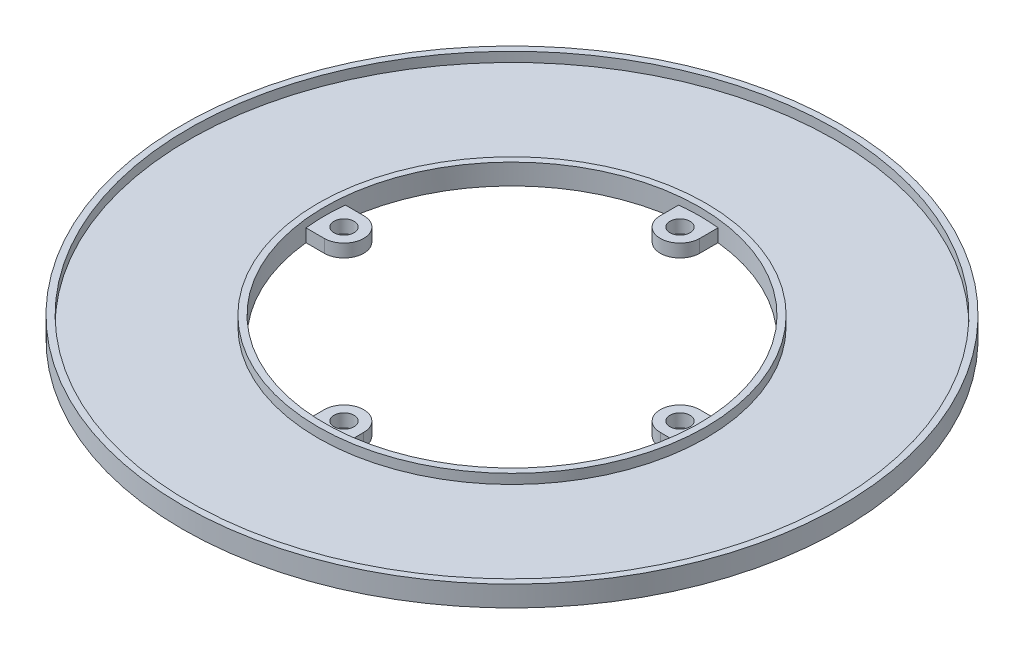
SolidWorks part; units mm, degrees
ref_plane "前视基准面" through (0, 0, 0) normal (0, 0, 1) x (1, 0, 0)
ref_plane "上视基准面" through (0, 0, 0) normal (0, 1, 0) x (1, 0, 0)
ref_plane "右视基准面" through (0, 0, 0) normal (1, 0, 0) x (0, 0, -1)
other "Configuration Table"
sketch "草图1" plane through (0, 0, 0) normal (0, 0, 1) x (1, 0, 0)
  line L0 (29, 0) -> (29, 3.2)
  line L1 (29, 3.2) -> (30, 3.2)
  line L2 (30, 3.2) -> (30, 1.7)
  line L3 (30, 1.7) -> (50, 1.7)
  line L4 (50, 1.7) -> (50, 3.2)
  line L5 (50, 3.2) -> (51, 3.2)
  line L6 (51, 3.2) -> (51, 0)
  line L7 (51, 0) -> (29, 0)
  line L8 (0, 0) -> (0, 3.2) construction
  point P2 (40, 1.7)
  point P9 (40, 0)
  point P11 (0, 0)
  dimension "D1" = 29
  dimension "D2" = 51
  dimension "D3" = 20
  dimension "D4" = 1.7
  dimension "D5" = 1.5
revolve "旋转1" add sketch "草图1" angle 360 about L8
sketch "草图2" plane through (0, 0, 0) normal (0, -1, 0) x (1, 0, 0)
  line L0 (-3.05, 26) -> (-3.05, 28.8392)
  line L1 (3.05, 26) -> (3.05, 28.8392)
  line L2 (26, 3.05) -> (28.8392, 3.05)
  line L3 (26, -3.05) -> (28.8392, -3.05)
  line L4 (3.05, -26) -> (3.05, -28.8392)
  line L5 (-3.05, -26) -> (-3.05, -28.8392)
  line L6 (-26, -3.05) -> (-28.8392, -3.05)
  line L7 (-26, 3.05) -> (-28.8392, 3.05)
  circle A4 centre (0, 26) radius 1.55
  circle A10 centre (0, 0) radius 29 construction
  arc A11 (-3.05, 26) -> (3.05, 26) centre (0, 26) ccw
  arc A12 (3.05, 28.8392) -> (-3.05, 28.8392) centre (0, 0) ccw
  circle A13 centre (26, 0) radius 1.55
  arc A14 (26, 3.05) -> (26, -3.05) centre (26, 0) ccw
  arc A15 (28.8392, -3.05) -> (28.8392, 3.05) centre (0, 0) ccw
  circle A16 centre (0, -26) radius 1.55
  arc A17 (3.05, -26) -> (-3.05, -26) centre (0, -26) ccw
  arc A18 (-3.05, -28.8392) -> (3.05, -28.8392) centre (0, 0) ccw
  circle A19 centre (-26, 0) radius 1.55
  arc A20 (-26, -3.05) -> (-26, 3.05) centre (-26, 0) ccw
  arc A21 (-28.8392, 3.05) -> (-28.8392, -3.05) centre (0, 0) ccw
  point P3 (0, 0)
  point P4 (0, 0)
  point P5 (0, 0)
  point P15 (0, 0)
  point P20 (0, 0)
  point P35 (0, 0)
  dimension "D4" = 4
  dimension "D1" = 1.5
  dimension "D2" = 3.1
  dimension "D3" = 26
extrude "凸台-拉伸1" add sketch "草图2" against normal blind 2 contours A11 L1 A12 L0 | A14 L3 A15 L2 | A17 L5 A18 L4 | A20 L7 A21 L6
extrude "切除-拉伸1" cut sketch "草图2<4>" against normal up to next contours A13 | A4 | A16 | A19
sketch "草图2<4>" plane through (0, 0, 0) normal (0, -1, 0) x (1, 0, 0) same geometry as "草图2"
